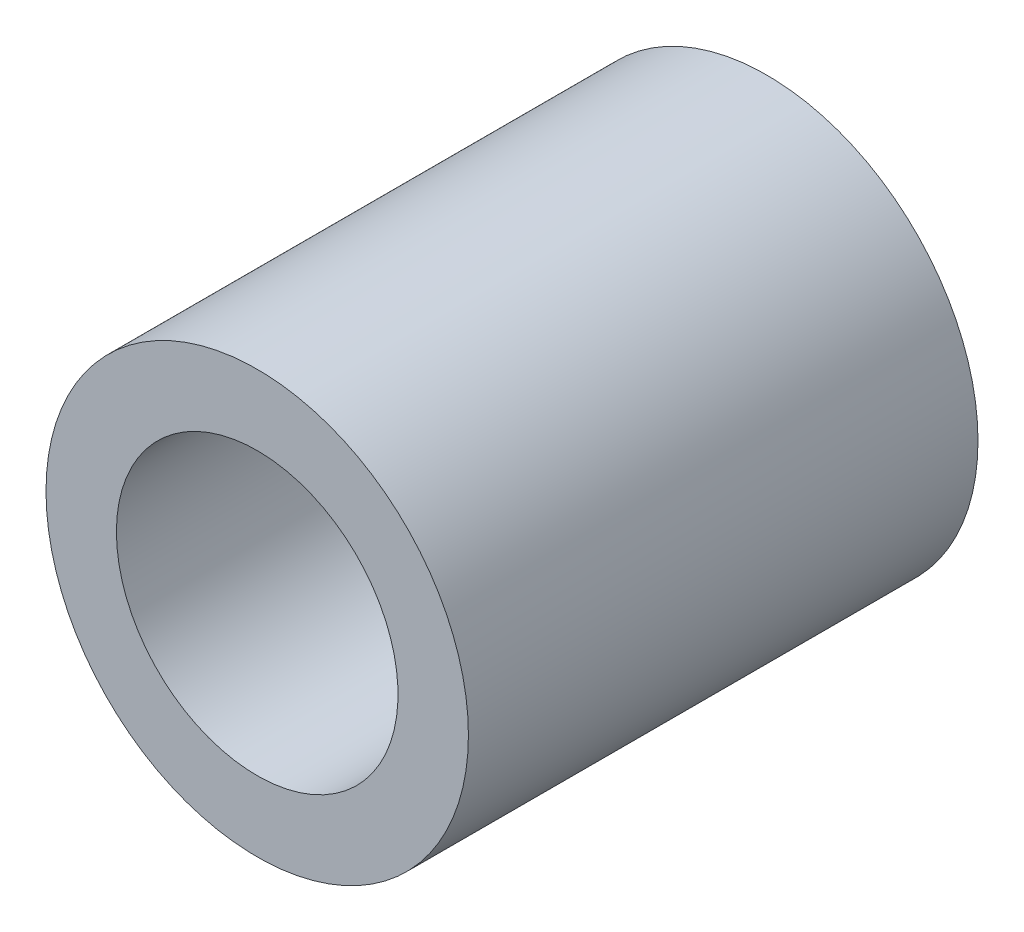
SolidWorks part; units mm, degrees
material "ABS"
ref_plane "Front Plane" through (0, 0, 0) normal (0, 0, 1) x (1, 0, 0)
ref_plane "Top Plane" through (0, 0, 0) normal (0, 1, 0) x (1, 0, 0)
ref_plane "Right Plane" through (0, 0, 0) normal (1, 0, 0) x (0, 0, -1)
sketch "Sketch1" plane through (0, 0, 0) normal (0, 0, 1) x (1, 0, 0)
  circle A0 centre (0, 0) radius 3.175
  circle A1 centre (0, 0) radius 4.7625
  dimension "D1" = 6.35
  dimension "D2" = 9.525
extrude "Boss-Extrude1" add sketch "Sketch1" along normal mid plane 11.4903
